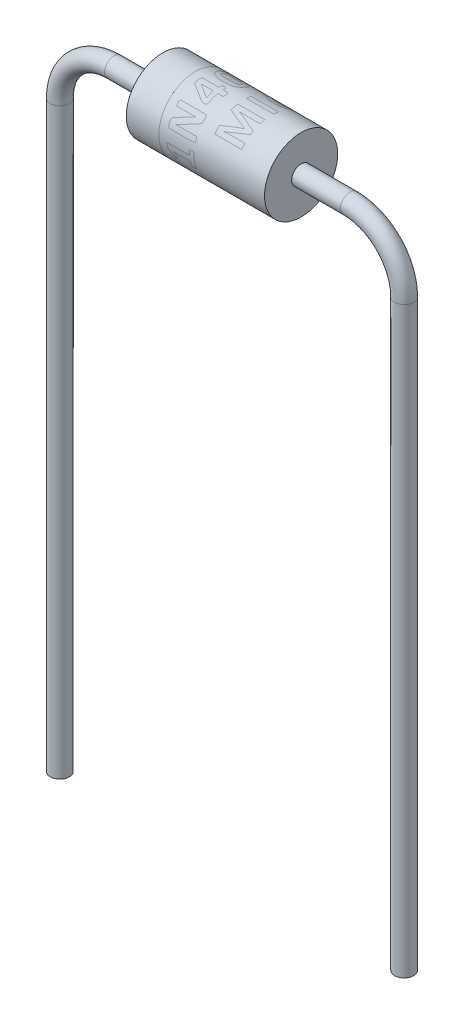
SolidWorks part; units mm, degrees
other "Diode"
other "Cathode Silver Band"
other "Wire"
ref_plane "Front Plane" through (0, 0, 0) normal (0, 0, 1) x (1, 0, 0)
ref_plane "Top Plane" through (0, 0, 0) normal (0, 1, 0) x (1, 0, 0)
ref_plane "Right Plane" through (0, 0, 0) normal (1, 0, 0) x (0, 0, -1)
sketch "Sketch1" plane through (0, 0, 0) normal (1, 0, 0) x (0, 0, -1)
  circle A0 centre (0, 0) radius 1.35
  circle A1 centre (0, 0) radius 0.35
  dimension "D1" = 2.7
  dimension "D2" = 0.7
extrude "Boss-Extrude1" add sketch "Sketch1" along normal mid plane 5.1
sketch "Sketch2" plane through (-2.55, 0, 0) normal (-1, 0, 0) x (0, 0, 1)
  circle A1 centre (0, 0) radius 1.35 construction
  circle A2 centre (0, 0) radius 1.34
  circle A3 centre (0, 0) radius 1.34
  circle A4 centre (0, 0) radius 1.35
  dimension "D1" = 0.01
extrude "Cut-Extrude1" cut sketch "Sketch2" against normal blind 1.2
sketch "Sketch3" plane through (-1.35, 0, 0) normal (-1, 0, 0) x (0, 0, 1)
  circle A0 centre (0, 0) radius 1.34 construction
  circle A1 centre (0, 0) radius 1.34
  circle A2 centre (0, 0) radius 1.35 construction
  circle A3 centre (0, 0) radius 1.35
extrude "Boss-Extrude2" add sketch "Sketch3" along normal up to surface (1.2 mm away) separate body up to face at (-2.55, 0, -0.35)
ref_plane "Plane1" through (0, 5, 0) normal (0, 1, 0) x (1, 0, 0)
sketch "Sketch4" plane through (0, 5, 0) normal (0, 1, 0) x (1, 0, 0)
  line L0 (-0.05, 7.5) -> (-0.05, -7.5) construction
  line L1 (-0.05, 0) -> (-2.55, 0) construction
  line L2 (-2.55, 1.35) -> (-2.55, -1.35) construction
  line L4 (-0.05, 0) -> (1.45, 0) construction
  line L5 (1.45, 7.5) -> (1.45, -7.5) construction
  text T0 "1N4004" font "Calibri" height 1
  text T1 "MIC" font "Corbel" height 1
  dimension "D1" = 2.5
  dimension "D2" = 15
  dimension "D3" = 1.5
wrap "Wrap1" sketch "Sketch4" wrap type scribe source sketch "Sketch4" face at (2.55, 0, -1.35)
sketch "Sketch5" plane through (0, 0, 0) normal (0, 0, 1) x (1, 0, 0)
  line L0 (0, 0) -> (-4.35, 0)
  line L1 (-6.35, -2) -> (-6.35, -23.5084)
  line L2 (0, 0) -> (4.35, 0)
  line L3 (6.35, -2) -> (6.35, -23.5084)
  arc A0 (-4.35, 0) -> (-6.35, -2) centre (-4.35, -2) ccw
  arc A1 (4.35, 0) -> (6.35, -2) centre (4.35, -2) cw
  dimension "D2" = 2
  dimension "D3" = 58
  dimension "D1" = 12.7
sketch "Sketch6" plane through (0, 0, 0) normal (1, 0, 0) x (0, 0, -1)
  circle A0 centre (0, 0) radius 0.35
  dimension "D1" = 0.7
sweep "Sweep1" add profiles "Sketch6" path "Sketch5"
